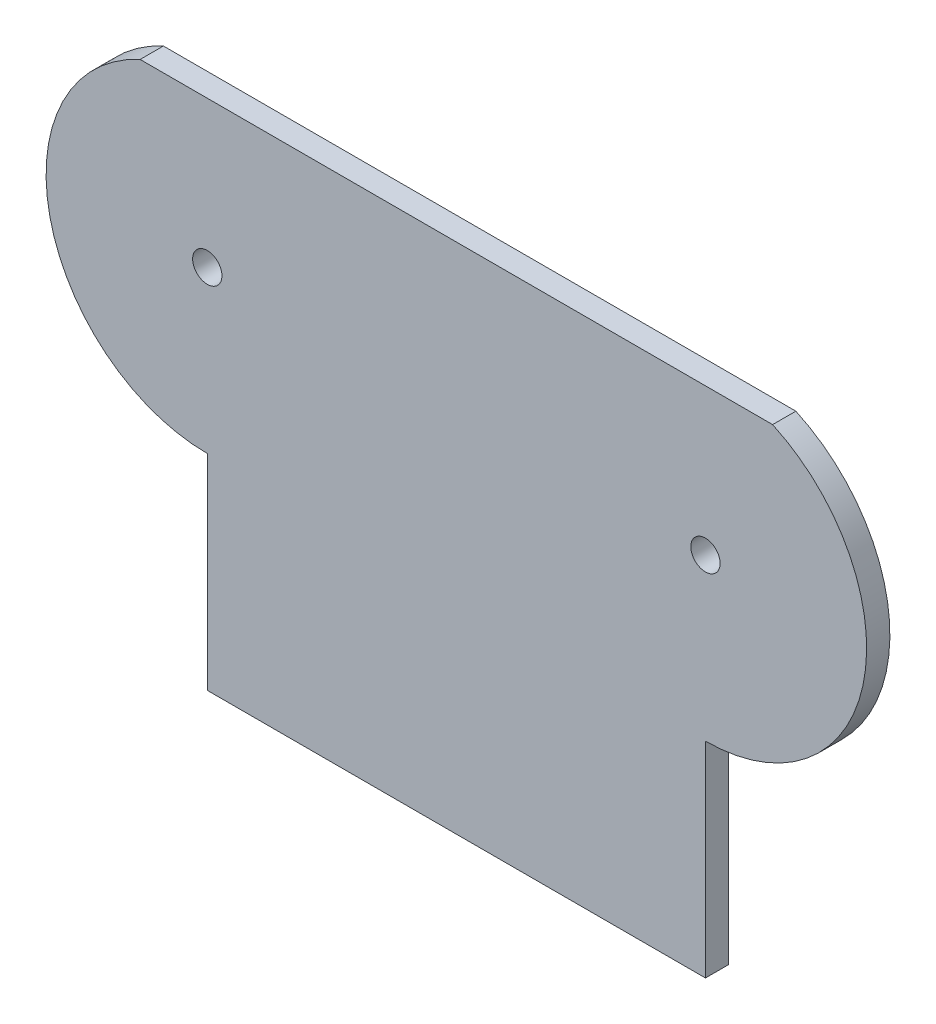
SolidWorks part; units mm, degrees
ref_plane "Front Plane" through (0, 0, 0) normal (0, 0, 1) x (1, 0, 0)
ref_plane "Top Plane" through (0, 0, 0) normal (0, 1, 0) x (1, 0, 0)
ref_plane "Right Plane" through (0, 0, 0) normal (1, 0, 0) x (0, 0, -1)
sketch "Sketch1" plane through (0, 0, 0) normal (0, 0, 1) x (1, 0, 0)
  line L0 (90, 70) -> (90, 0) construction
  line L1 (56, 0) -> (124, 0)
  line L2 (0, 0) -> (0, 70) construction
  line L3 (46.8348, 70) -> (133.1652, 70)
  line L4 (180, 0) -> (180, 70) construction
  line L5 (56, 28) -> (56, 0)
  line L6 (124, 28) -> (124, 0)
  line L7 (0, 70) -> (46.8348, 70) construction
  line L8 (133.1652, 70) -> (180, 70) construction
  line L9 (0, 0) -> (56, 0) construction
  line L10 (124, 0) -> (180, 0) construction
  circle A0 centre (56, 50) radius 2
  circle A1 centre (124, 50) radius 2
  arc A2 (46.8348, 70) -> (56, 28) centre (56, 50) ccw
  arc A3 (133.1652, 70) -> (124, 28) centre (124, 50) cw
  point P17 (0, 0)
  point P18 (0, 0)
  point P19 (56, 28)
  point P20 (0, 0)
  point P21 (0, 0)
  point P22 (133.1652, 70)
  point P23 (123.1979, 0)
  dimension "D3" = 4
  dimension "D7" = 46.8348
  dimension "D8" = 22
  dimension "D1" = 70
  dimension "D2" = 180
  dimension "D4" = 68
  dimension "D5" = 34
  dimension "D6" = 50
extrude "Boss-Extrude1" add sketch "Sketch1" along normal blind 3.175
